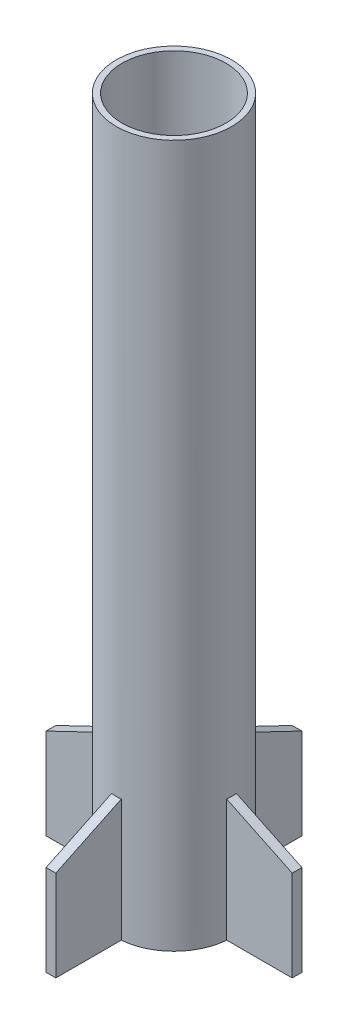
SolidWorks part; units mm, degrees
ref_plane "Front Plane" through (0, 0, 0) normal (0, 0, 1) x (1, 0, 0)
ref_plane "Top Plane" through (0, 0, 0) normal (0, 1, 0) x (1, 0, 0)
ref_plane "Right Plane" through (0, 0, 0) normal (1, 0, 0) x (0, 0, -1)
sketch "Sketch1" plane through (0, 0, 0) normal (0, 1, 0) x (1, 0, 0)
  circle A0 centre (0, 0) radius 9.525
  circle A1 centre (0, 0) radius 11.925
  dimension "D1" = 19.05
  dimension "D2" = 2.4
extrude "Boss-Extrude1" add sketch "Sketch1" along normal blind 145
sketch "Sketch2" plane through (0, 0, 0) normal (0, 0, 1) x (1, 0, 0)
  line L9 (-9.525, 0) -> (-9.525, 0.375)
  line L10 (-9.525, 0.375) -> (-6.3975, 0.375)
  line L11 (-6.3975, 0.375) -> (-6.3975, 25.875)
  line L12 (-6.3975, 25.875) -> (-9.525, 25.875)
  line L13 (-9.525, 25.875) -> (-9.525, 26.25)
  line L14 (-9.525, 26.25) -> (-9.7801, 26.25)
  line L15 (-9.7801, 26.25) -> (-25.4051, 18.75)
  line L16 (-25.4051, 18.75) -> (-25.4051, 0)
  line L17 (-25.4051, 0) -> (-9.525, 0)
  line L18 (0, 0) -> (-9.525, 0) construction
extrude "Boss-Extrude2" add sketch "Sketch2" along normal blind 1 and the other way blind 1
pattern_circular "CirPattern1" count 4 over 360 about axis through (0, 145, 0) along (0, -1, 0) of "Boss-Extrude2" reverse direction yes
sketch "Sketch3" plane through (0, 0, 0) normal (0, -1, 0) x (1, 0, 0)
  circle A0 centre (0, 0) radius 6.125
  circle A1 centre (0, 0) radius 7.325
  dimension "D1" = 12.25
  dimension "D2" = 1.2
extrude "Boss-Extrude3" add sketch "Sketch3" against normal blind 87.75 separate body
sketch "Sketch4" plane through (0, 145, 0) normal (0, 1, 0) x (1, 0, 0)
  circle A0 centre (0, 0) radius 10.725
  circle A1 centre (0, 0) radius 9.525 construction
  circle A2 centre (0, 0) radius 9.525
  dimension "D1" = 1.2
extrude "Cut-Extrude1" cut sketch "Sketch4" against normal blind 19
sketch "Sketch5" plane through (0, 87.75, 0) normal (0, 1, 0) x (1, 0, 0)
  circle A0 centre (0, 0) radius 6.125
  circle A1 centre (0, 0) radius 9.525 construction
  circle A2 centre (0, 0) radius 9.525
extrude "Boss-Extrude4" add sketch "Sketch5" against normal blind 1
ref_plane "Plane1" through (0, 43.875, 0) normal (0, 1, 0) x (1, 0, 0)
sketch "Sketch6" plane through (0, 43.875, 0) normal (0, 1, 0) x (1, 0, 0)
  circle A0 centre (0, 0) radius 9.525 construction
  circle A1 centre (0, 0) radius 6.125 construction
  circle A2 centre (0, 0) radius 9.525
  circle A3 centre (0, 0) radius 6.125
extrude "Boss-Extrude5" add sketch "Sketch6" along normal blind 0.5 and the other way blind 0.5
sketch "Sketch7" plane through (0, 0, 0) normal (0, -1, 0) x (1, 0, 0)
  circle A0 centre (0, 0) radius 6.125 construction
  circle A1 centre (0, 0) radius 9.525 construction
  circle A2 centre (0, 0) radius 6.125
  circle A3 centre (0, 0) radius 9.525
extrude "Boss-Extrude6" add sketch "Sketch7" against normal blind 1
